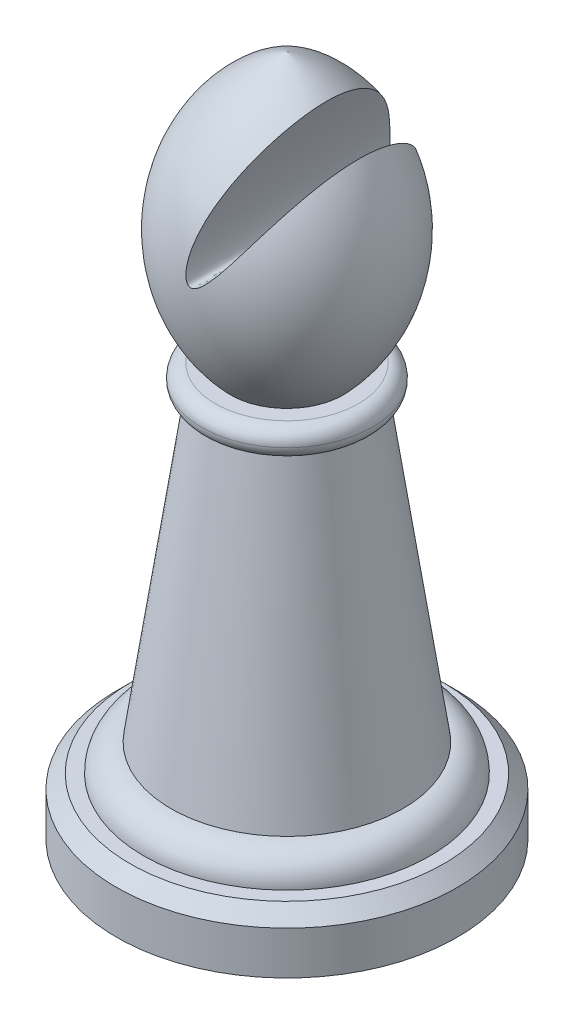
SolidWorks part; units mm, degrees
ref_plane "Front Plane" through (0, 0, 0) normal (0, 0, 1) x (1, 0, 0)
ref_plane "Top Plane" through (0, 0, 0) normal (0, 1, 0) x (1, 0, 0)
ref_plane "Right Plane" through (0, 0, 0) normal (1, 0, 0) x (0, 0, -1)
sketch "Sketch2" plane through (0, 0, 0) normal (0, 0, 1) x (1, 0, 0)
  line L0 (0, 0) -> (0, 38.1) construction
  line L1 (-6.477, 3.175) -> (-6.477, 4.699) construction
  line L2 (0, 0) -> (-9.525, 0)
  line L4 (-8.001, 3.175) -> (-9.525, 3.175)
  line L5 (-9.525, 0) -> (-9.525, 3.175)
  line L8 (-6.477, 4.699) -> (-8.001, 4.699)
  line L9 (-8.001, 3.175) -> (-8.001, 4.699)
  line L10 (-4.0386, 21.5392) -> (-9.525, 21.5392) construction
  line L11 (-6.477, 4.699) -> (-4.0386, 21.5392)
  line L12 (0, 21.5392) -> (-9.525, 21.5392) construction
  line L13 (-4.0386, 21.5392) -> (-4.7625, 21.5392)
  line L16 (-4.7625, 21.5392) -> (-4.7625, 23.0632)
  line L17 (-4.7625, 23.0632) -> (-3.1496, 23.0632)
  line L18 (0, 0) -> (0, 38.1)
  arc A0 (-3.1496, 23.0632) -> (0, 38.1) centre (3.5473, 29.5087) cw
  point P9 (-8.001, 3.937)
  point P18 (-3.1496, 23.0632)
  dimension "D1" = 38.1
  dimension "D2" = 9.525
  dimension "D3" = 3.175
  dimension "D4" = 1.524
  dimension "D5" = 1.524
  dimension "D9" = 1.524
  dimension "D6" = 1.524
  dimension "D7" = 21.5392
revolve "Revolve1" add sketch "Sketch2" angle 360 about L18
fillet "Fillet1" radius 0.762 2 edges at (0, 23.0632, -4.7625) (0, 21.5392, -4.7625)
fillet "Fillet2" radius 1.524 1 edges at (0, 4.699, -8.001)
chamfer "Chamfer1" distance 0.762 angle 45 1 edges at (0, 3.175, -9.525)
sketch "Sketch4" plane through (0, 0, 0) normal (0, 0, 1) x (1, 0, 0)
  arc A0 (3.1496, 23.0632) -> (0, 38.1) centre (-3.5473, 29.5087) ccw construction
  ellipse E0 centre (3.1541, 35.9496) end of major axis (6.0381, 42.1577) minor radius 1.2192
  point P1 (0, 0)
  point P7 (0, 0)
  point P11 (0, 0)
  point P12 (0, 0)
  point P13 (-0.4279, 29.1541)
  point P14 (0, 0)
  point P16 (0, 29.16)
  dimension "D1" = 2.4384
  dimension "D2" = 13.6906
extrude "Cut-Extrude1" cut sketch "Sketch4" against normal through all both and the other way through all
